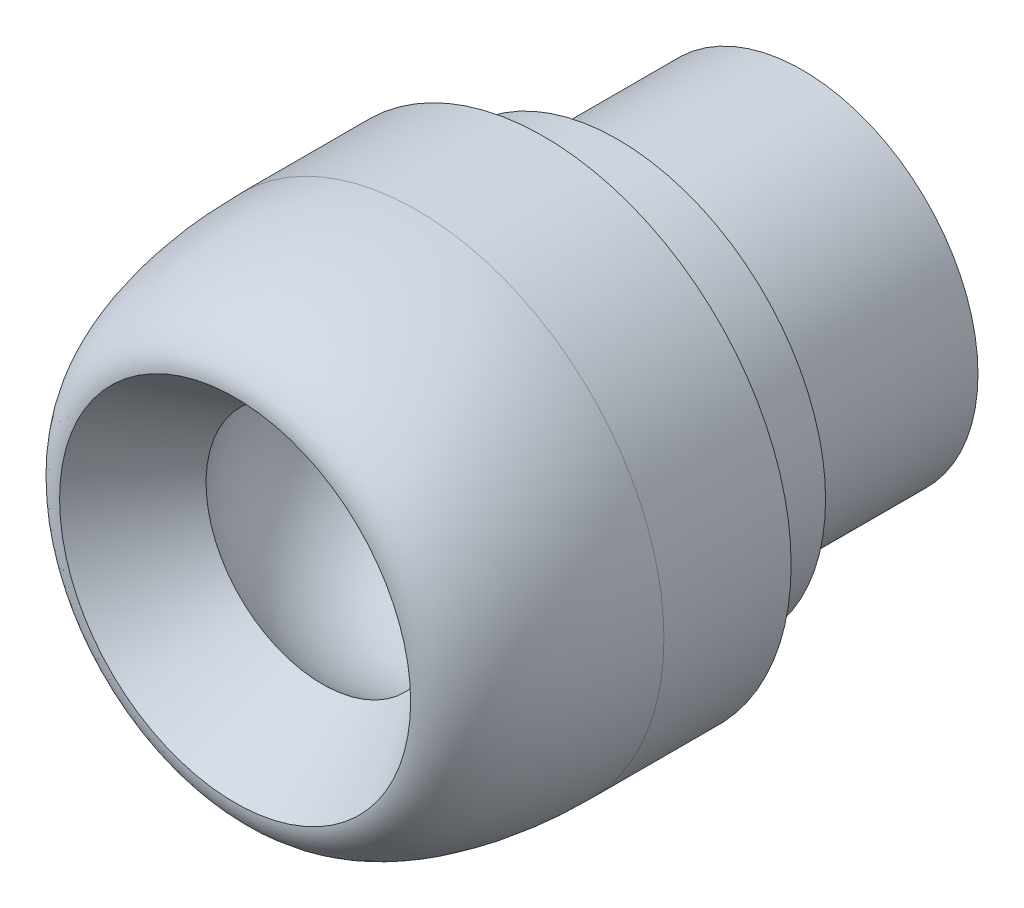
SolidWorks part; units mm, degrees
ref_plane "Front Plane" through (0, 0, 0) normal (0, 0, 1) x (1, 0, 0)
ref_plane "Top Plane" through (0, 0, 0) normal (0, 1, 0) x (1, 0, 0)
ref_plane "Right Plane" through (0, 0, 0) normal (1, 0, 0) x (0, 0, -1)
sketch "Sketch1" plane through (0, 0, 0) normal (1, 0, 0) x (0, 0, -1)
  line L0 (-40.2127, 0) -> (145.9468, 0) construction
  line L2 (-6, 8) -> (-12, 12.065)
  line L3 (9.4133, 3.375) -> (27, 3.375)
  line L4 (27, 3.375) -> (27, 12.065)
  line L5 (27, 12.065) -> (14.3, 12.065)
  line L6 (14.3, 12.065) -> (14.3, 14.2875)
  line L7 (9.22, 17) -> (0.4737, 17)
  line L8 (14.3, 14.2875) -> (9.22, 14.2875)
  line L9 (9.22, 14.2875) -> (9.22, 17)
  arc A0 (9.4133, 3.375) -> (-6, 8) centre (0, 0) ccw
  ellipse E0 centre (0.4737, 12.065) end of major axis (-12, 12.065) minor radius 4.935 (-12, 12.065) -> (0.4737, 17) cw
  point P3 (0, 0)
  dimension "D1" = 20
  dimension "D2" = 6.75
  dimension "D3" = 12
  dimension "D4" = 24.13
  dimension "D5" = 39
  dimension "D6" = 12.7
  dimension "D7" = 24.13
  dimension "D8" = 5.08
  dimension "D9" = 28.575
  dimension "D10" = 16
  dimension "D11" = 34
  dimension "D12" = 12.4737
  dimension "D13" = 0.4737
revolve "Revolve1" add sketch "Sketch1" angle 360 about L0
thread "Thread1" pitch 1.5 method cut profile "Thread Profile1" start angle 0, offset 0, length 15, pitch 1.5, diameter 6.75
ref_plane "Plane1" through (3.375, 0, -27) normal (0, -1, 0) x (1, 0, 0)
sketch "Thread Profile1" plane through (3.375, 0, -27) normal (0, -1, 0) x (1, 0, 0)
  line L0 (0, 0) -> (0, 1.5) construction
  line L1 (0, 0) -> (0.8119, 0.4687)
  line L2 (0.8119, 0.4687) -> (0.8119, 0.6562)
  line L3 (0.8119, 0.6562) -> (0, 1.125)
  line L4 (0.8119, 0.5625) -> (0, 0.5625) construction
  line L11 (0, 0) -> (0, 1.125)
  point P2 (0, 0)
  dimension "Pitch" = 1.5
  dimension "Profile_Angle" = 60
  dimension "Profile_Land" = 0.1875
  dimension "Profile_Height" = 0.8119
chamfer "Chamfer1" distance 0.7 angle 45 1 edges at (3.375, 0, -27)
sketch3d "3DSketch1"
  line L0 (0, 0, -145.9468) -> (0, 0, 40.2127) construction
  line L1 (0, 0, -401) -> (0, 0, 0) construction
  point P4 (0, 0, 0)
  dimension "D1" = 401
